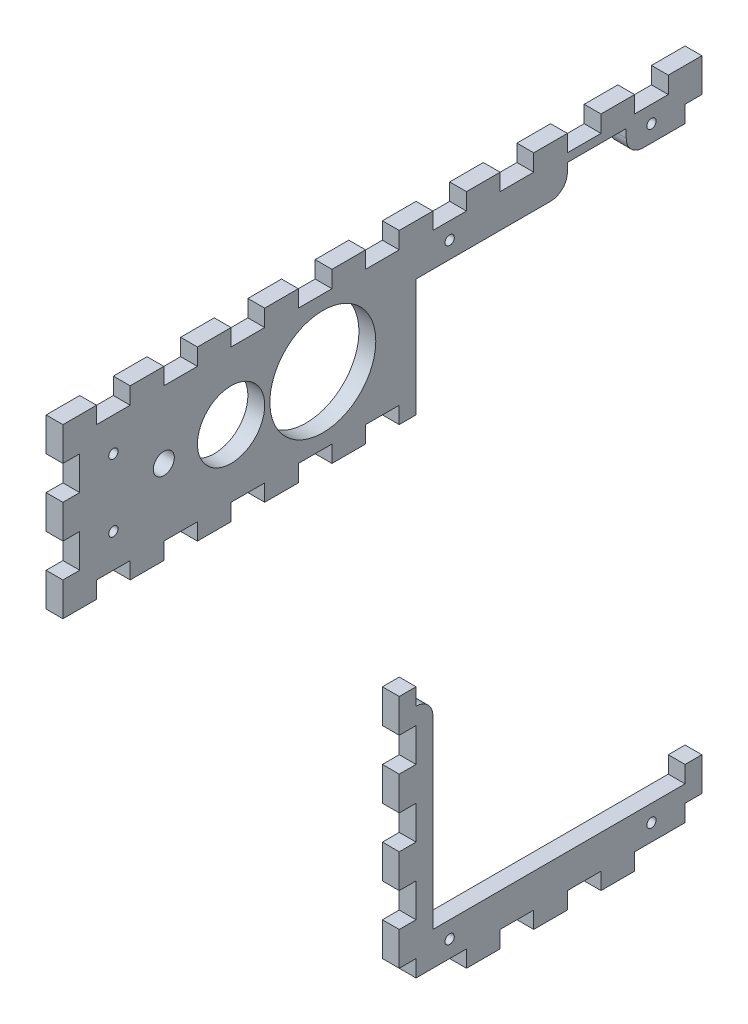
SolidWorks part; units mm, degrees
material "Pine"
ref_plane "Front Plane" through (0, 0, 0) normal (0, 0, 1) x (1, 0, 0)
ref_plane "Top Plane" through (0, 0, 0) normal (0, 1, 0) x (1, 0, 0)
ref_plane "Right Plane" through (0, 0, 0) normal (1, 0, 0) x (0, 0, -1)
sketch "Sketch1" plane through (0, 0, 0) normal (1, 0, 0) x (0, 0, -1)
  line L0 (0, 0) -> (0, 190.5)
  line L1 (0, 190.5) -> (-127, 190.5)
  line L2 (-127, 190.5) -> (-127, 254)
  line L3 (-127, 254) -> (114.3, 254)
  line L4 (114.3, 254) -> (114.3, 0)
  line L5 (114.3, 0) -> (0, 0)
  line L7 (-107.95, 234.95) -> (95.25, 234.95) construction
  line L8 (-107.95, 234.95) -> (-107.95, 209.55) construction
  line L9 (-107.95, 209.55) -> (95.25, 209.55) construction
  line L10 (95.25, 234.95) -> (95.25, 209.55) construction
  line L11 (95.25, 234.95) -> (19.05, 234.95) construction
  line L12 (95.25, 234.95) -> (95.25, 12.7) construction
  line L13 (95.25, 12.7) -> (19.05, 12.7) construction
  line L14 (19.05, 234.95) -> (19.05, 12.7) construction
  circle A0 centre (-107.95, 234.95) radius 1.75
  circle A1 centre (-107.95, 209.55) radius 1.75
  circle A2 centre (19.05, 241.3) radius 1.75
  circle A3 centre (95.25, 241.3) radius 1.75
  circle A4 centre (19.05, 12.7) radius 1.75
  circle A5 centre (95.25, 12.7) radius 1.75
  dimension "D11" = 3.5
  dimension "D1" = 114.3
  dimension "D2" = 254
  dimension "D3" = 241.3
  dimension "D4" = 63.5
  dimension "D5" = 25.4
  dimension "D6" = 76.2
  dimension "D7" = 196.85
  dimension "D8" = 127
  dimension "D9" = 19.05
  dimension "D10" = 19.05
  dimension "D12" = 6.35
  dimension "D13" = 6.35
extrude "Boss-Extrude1" add sketch "Sketch1" along normal blind 6.35
sketch "Sketch2" plane through (6.35, 0, 0) normal (1, 0, 0) x (0, 0, -1)
  line L0 (114.3, 254) -> (-127, 254) construction
  line L1 (-114.3, 254) -> (-101.6, 254)
  line L2 (-114.3, 254) -> (-114.3, 247.65)
  line L3 (-114.3, 247.65) -> (-101.6, 247.65)
  line L4 (-101.6, 254) -> (-101.6, 247.65)
  line L5 (-127, 254) -> (-127, 190.5) construction
  dimension "D1" = 12.7
  dimension "D2" = 6.35
  dimension "D3" = 12.7
extrude "Cut-Extrude1" cut sketch "Sketch2" against normal through all
pattern_linear "LPattern1" count 10 spacing 25.4 along (0, 0, -1) of "Cut-Extrude1"
sketch "Sketch3" plane through (6.35, 0, 0) normal (1, 0, 0) x (0, 0, -1)
  line L0 (114.3, 0) -> (114.3, 254) construction
  line L1 (114.3, 241.3) -> (107.95, 241.3)
  line L2 (114.3, 241.3) -> (114.3, 228.6)
  line L3 (114.3, 228.6) -> (107.95, 228.6)
  line L4 (107.95, 241.3) -> (107.95, 228.6)
  line L5 (114.3, 254) -> (101.6, 254) construction
  line L6 (101.6, 247.65) -> (101.6, 254) construction
  line L7 (88.9, 247.65) -> (101.6, 247.65) construction
  dimension "D1" = 12.7
extrude "Cut-Extrude2" cut sketch "Sketch3" against normal through all
pattern_linear "LPattern2" count 10 spacing 25.4 along (0, -1, 0) of "Cut-Extrude2"
sketch "Sketch4" plane through (6.35, 0, 0) normal (1, 0, 0) x (0, 0, -1)
  line L0 (-127, 254) -> (-127, 190.5) construction
  line L1 (-127, 241.3) -> (-120.65, 241.3)
  line L2 (-127, 241.3) -> (-127, 228.6)
  line L3 (-127, 228.6) -> (-120.65, 228.6)
  line L4 (-120.65, 241.3) -> (-120.65, 228.6)
  line L5 (-114.3, 254) -> (-127, 254) construction
  line L6 (-127, 215.9) -> (-120.65, 215.9)
  line L7 (-127, 215.9) -> (-127, 203.2)
  line L8 (-127, 203.2) -> (-120.65, 203.2)
  line L9 (-120.65, 215.9) -> (-120.65, 203.2)
  line L10 (-114.3, 247.65) -> (-101.6, 247.65) construction
  dimension "D1" = 12.7
  dimension "D2" = 12.7
  dimension "D3" = 6.35
extrude "Cut-Extrude3" cut sketch "Sketch4" against normal through all
sketch "Sketch5" plane through (6.35, 0, 0) normal (1, 0, 0) x (0, 0, -1)
  line L0 (-127, 190.5) -> (0, 190.5) construction
  line L1 (-114.3, 190.5) -> (-101.6, 190.5)
  line L2 (-114.3, 190.5) -> (-114.3, 196.85)
  line L3 (-114.3, 196.85) -> (-101.6, 196.85)
  line L4 (-101.6, 190.5) -> (-101.6, 196.85)
  line L5 (-127, 203.2) -> (-127, 190.5) construction
  line L6 (-114.3, 247.65) -> (-101.6, 247.65) construction
  line L7 (-127, 203.2) -> (-120.65, 203.2) construction
  dimension "D1" = 12.7
extrude "Cut-Extrude4" cut sketch "Sketch5" against normal through all
pattern_linear "LPattern3" count 5 spacing 25.4 along (0, 0, -1) of "Cut-Extrude4"
sketch "Sketch6" plane through (6.35, 0, 0) normal (1, 0, 0) x (0, 0, -1)
  line L0 (114.3, 12.7) -> (107.95, 12.7) construction
  line L1 (0, 0) -> (6.35, 0)
  line L2 (0, 0) -> (0, 12.7)
  line L3 (0, 12.7) -> (6.35, 12.7)
  line L4 (6.35, 0) -> (6.35, 12.7)
extrude "Cut-Extrude5" cut sketch "Sketch6" against normal through all
pattern_linear "LPattern4" count 8 spacing 25.4 along (0, 1, 0) of "Cut-Extrude5"
sketch "Sketch7" plane through (6.35, 0, 0) normal (1, 0, 0) x (0, 0, -1)
  line L0 (6.35, 0) -> (107.95, 0) construction
  line L1 (12.7, 0) -> (25.4, 0)
  line L2 (12.7, 0) -> (12.7, 6.35)
  line L3 (12.7, 6.35) -> (25.4, 6.35)
  line L4 (25.4, 0) -> (25.4, 6.35)
  line L5 (6.35, 0) -> (6.35, 12.7) construction
  line L6 (38.1, 0) -> (50.8, 0)
  line L7 (38.1, 0) -> (38.1, 6.35)
  line L8 (38.1, 6.35) -> (50.8, 6.35)
  line L9 (50.8, 0) -> (50.8, 6.35)
  line L10 (63.5, 0) -> (76.2, 0)
  line L11 (63.5, 0) -> (63.5, 6.35)
  line L12 (63.5, 6.35) -> (76.2, 6.35)
  line L13 (76.2, 0) -> (76.2, 6.35)
  line L14 (6.35, 12.7) -> (0, 12.7) construction
  line L16 (88.9, 0) -> (101.6, 0)
  line L17 (88.9, 0) -> (88.9, 6.35)
  line L18 (88.9, 6.35) -> (101.6, 6.35)
  line L19 (101.6, 0) -> (101.6, 6.35)
  dimension "D1" = 6.35
  dimension "D2" = 12.7
  dimension "D3" = 12.7
  dimension "D4" = 12.7
extrude "Cut-Extrude6" cut sketch "Sketch7" against normal through all
sketch "Sketch8" plane through (6.35, 0, 0) normal (1, 0, 0) x (0, 0, -1)
  line L1 (12.7, 6.35) -> (6.35, 6.35)
  line L2 (12.7, 6.35) -> (12.7, 0)
  line L3 (12.7, 0) -> (6.35, 0)
  line L4 (6.35, 6.35) -> (6.35, 0)
  line L5 (101.6, 6.35) -> (107.95, 6.35)
  line L6 (101.6, 6.35) -> (101.6, 0)
  line L7 (101.6, 0) -> (107.95, 0)
  line L8 (107.95, 6.35) -> (107.95, 0)
extrude "Cut-Extrude7" cut sketch "Sketch8" against normal through all
sketch "Sketch9" plane through (6.35, 0, 0) normal (1, 0, 0) x (0, 0, -1)
  line L0 (6.35, 152.4) -> (6.35, 165.1) construction
  line L1 (12.7, 234.95) -> (101.6, 234.95)
  line L2 (12.7, 234.95) -> (12.7, 19.05)
  line L3 (12.7, 19.05) -> (101.6, 19.05)
  line L4 (101.6, 234.95) -> (101.6, 19.05)
  line L5 (107.95, 165.1) -> (107.95, 152.4) construction
  line L6 (88.9, 247.65) -> (101.6, 247.65) construction
  circle A1 centre (19.05, 12.7) radius 1.75 construction
  dimension "D4" = 6.35
  dimension "D1" = 6.35
  dimension "D2" = 6.35
  dimension "D3" = 12.7
extrude "Cut-Extrude8" cut sketch "Sketch9" against normal through all
sketch "Sketch10" plane through (6.35, 0, 0) normal (1, 0, 0) x (0, 0, -1)
  line L0 (-101.6, 190.5) -> (-88.9, 190.5) construction
  line L1 (-127, 228.6) -> (-127, 215.9) construction
  circle A0 centre (-88.9, 222.25) radius 3.9687
  dimension "D1" = 31.75
  dimension "D2" = 38.1
  dimension "D3" = 7.9375
extrude "Cut-Extrude9" cut sketch "Sketch10" against normal through all
sketch "Sketch12" plane through (6.35, 0, 0) normal (1, 0, 0) x (0, 0, -1)
  line L0 (-88.9, 222.25) -> (-63.5, 222.25) construction
  circle A0 centre (-63.5, 222.25) radius 12.7
  dimension "D2" = 25.4
  dimension "D1" = 25.4
extrude "Cut-Extrude11" cut sketch "Sketch12" against normal through all
sketch "Sketch13" plane through (6.35, 0, 0) normal (1, 0, 0) x (0, 0, -1)
  line L0 (-63.5, 222.25) -> (-28.85, 222.25) construction
  line L2 (0, 196.85) -> (0, 190.5) construction
  circle A0 centre (-28.85, 222.25) radius 20
  dimension "D2" = 40
  dimension "D1" = 28.85
extrude "Cut-Extrude12" cut sketch "Sketch13" against normal through all
sketch "Sketch14" plane through (6.35, 0, 0) normal (1, 0, 0) x (0, 0, -1)
  line L1 (63.5, 244.475) -> (85.725, 244.475)
  line L2 (63.5, 244.475) -> (63.5, 234.95)
  line L3 (63.5, 234.95) -> (85.725, 234.95)
  line L4 (85.725, 244.475) -> (85.725, 234.95)
  line L5 (107.95, 234.95) -> (101.6, 234.95)
  line L6 (107.95, 234.95) -> (107.95, 19.05)
  line L7 (107.95, 19.05) -> (101.6, 19.05)
  line L8 (101.6, 234.95) -> (101.6, 19.05)
  line L9 (6.35, 234.95) -> (12.7, 234.95)
  line L10 (6.35, 234.95) -> (6.35, 95.25)
  line L11 (6.35, 95.25) -> (12.7, 95.25)
  line L12 (12.7, 234.95) -> (12.7, 95.25)
  line L13 (12.7, 234.95) -> (12.7, 19.05) construction
  line L14 (3.175, 95.25) -> (6.35, 95.25) construction
  line L15 (85.725, 241.3) -> (85.725, 244.475) construction
  line L16 (101.6, 19.05) -> (101.6, 234.95) construction
  line L17 (12.7, 19.05) -> (107.95, 19.05) construction
  line L18 (101.6, 234.95) -> (12.7, 234.95) construction
extrude "Cut-Extrude14" cut sketch "Sketch14" against normal through all contours L12 L9 L10 L11 | L4 L1 L2 L3 | L6 L7 L8 L5 region at (6.35, 239.7125, -74.6125) region at (6.35, 165.1, -9.525)
sketch "Sketch15" plane through (6.35, 0, 0) normal (1, 0, 0) x (0, 0, -1)
  line L1 (107.95, 63.5) -> (114.3, 63.5)
  line L2 (107.95, 63.5) -> (107.95, 165.1)
  line L3 (107.95, 165.1) -> (114.3, 165.1)
  line L4 (114.3, 63.5) -> (114.3, 165.1)
extrude "Cut-Extrude15" cut sketch "Sketch15" against normal through all
fillet "Fillet1" radius 6.35 2 edges at (3.175, 234.95, -85.725) (3.175, 234.95, -63.5)
sketch "Sketch16" plane through (6.35, 0, 0) normal (1, 0, 0) x (0, 0, -1)
  line L1 (96.7994, 231.0612) -> (126.4219, 231.0612)
  line L2 (96.7994, 231.0612) -> (96.7994, 36.2832)
  line L3 (96.7994, 36.2832) -> (126.4219, 36.2832)
  line L4 (126.4219, 231.0612) -> (126.4219, 36.2832)
  line L5 (-13.9806, 183.9898) -> (24.1635, 183.9898)
  line L6 (-13.9806, 183.9898) -> (-13.9806, 110.1365)
  line L7 (-13.9806, 110.1365) -> (24.1635, 110.1365)
  line L8 (24.1635, 183.9898) -> (24.1635, 110.1365)
extrude "Cut-Extrude16" cut sketch "Sketch16" against normal through all
fillet "Fillet2" radius 6.35 1 edges at (3.175, 95.25, -12.7)
